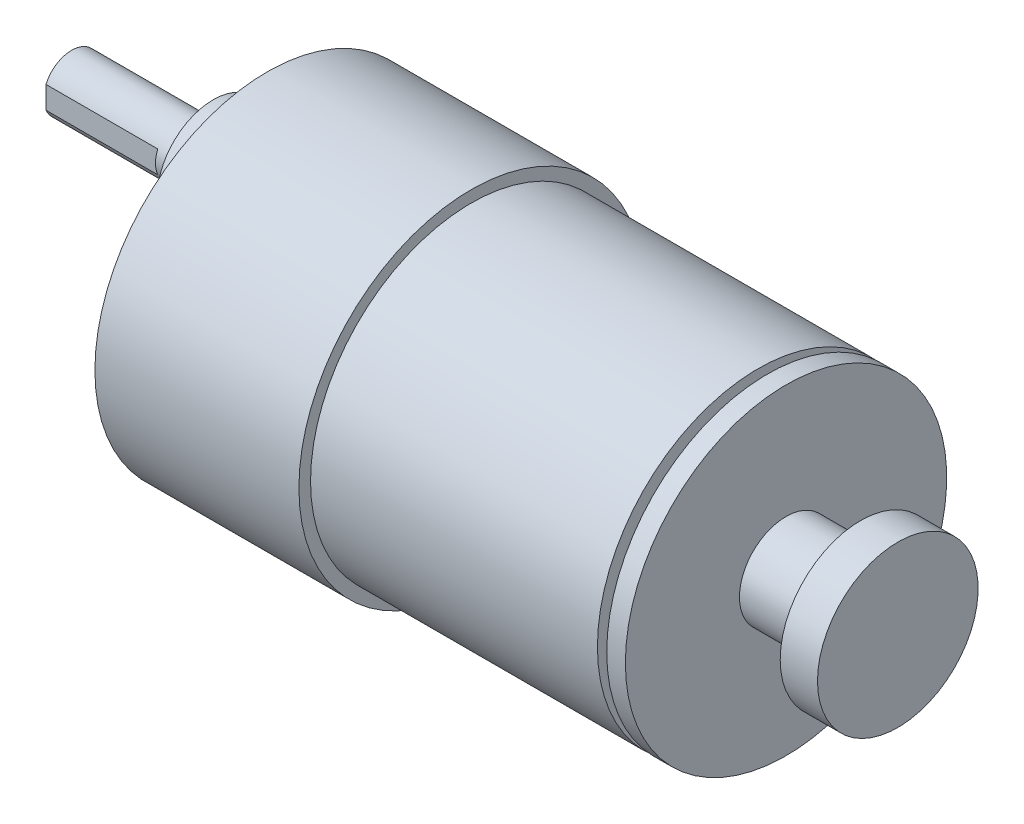
SolidWorks part; units mm, degrees
ref_plane "Front Plane" through (0, 0, 0) normal (0, 0, 1) x (1, 0, 0)
ref_plane "Top Plane" through (0, 0, 0) normal (0, 1, 0) x (1, 0, 0)
ref_plane "Right Plane" through (0, 0, 0) normal (1, 0, 0) x (0, 0, -1)
sketch "Sketch1" plane through (0, 0, 0) normal (0, 0, 1) x (1, 0, 0)
  line L0 (-80.1114, 0) -> (59.0183, 0) construction
  line L1 (0, 0) -> (0, 8.625)
  line L2 (0, 8.625) -> (-4, 8.625)
  line L3 (-4, 8.625) -> (-4, 5)
  line L4 (-4, 5) -> (-12, 5)
  line L5 (-12, 5) -> (-12, 17.25)
  line L6 (-12, 17.25) -> (-14, 17.25)
  line L7 (-14, 17.25) -> (-14, 5)
  line L8 (-14, 5) -> (-15, 5)
  line L9 (-15, 5) -> (-15, 17.25)
  line L10 (-15, 17.25) -> (-45.8, 17.25)
  line L11 (-45.8, 17.25) -> (-45.8, 18.5)
  line L12 (-45.8, 18.5) -> (-67.7, 18.5)
  line L13 (-67.7, 18.5) -> (-67.7, 0)
  line L14 (-67.7, 0) -> (0, 0)
  point P5 (0, 0)
  point P18 (0, 0)
  point P19 (0, 0)
  point P20 (0, 0)
  dimension "D1" = 34.5
  dimension "D2" = 30.8
  dimension "D3" = 37
  dimension "D4" = 21.9
  dimension "D5" = 15
  dimension "D6" = 17.25
  dimension "D7" = 1
  dimension "D8" = 2
  dimension "D9" = 10
  dimension "D10" = 4
revolve "MainBody" add sketch "Sketch1" angle 360 about L0
sketch "Sketch3" plane through (0, 0, 0) normal (0, 0, 1) x (1, 0, 0)
  line L0 (0, 0) -> (-101.2302, 0) construction
  line L1 (0, 7) -> (-101.2302, 7) construction
  line L2 (-67.7, 7) -> (-67.7, 13)
  line L4 (-67.7, 18.5) -> (-67.7, -18.5) construction
  line L5 (-67.7, 13) -> (-73.5, 13)
  line L6 (-73.5, 13) -> (-73.5, 10)
  line L7 (-73.5, 10) -> (-88.7, 10)
  line L8 (-88.7, 10) -> (-88.7, 7)
  line L9 (-88.7, 7) -> (-67.7, 7)
  dimension "D2" = 12
  dimension "D3" = 6
  dimension "D4" = 5.8
  dimension "D5" = 21
  dimension "D1" = 7
revolve "SmallBoss" add sketch "Sketch3" angle 360 about L1
sketch "Sketch4" plane through (-88.7, 0, 0) normal (-1, 0, 0) x (0, 0, 1)
  line L1 (-2.75, 10.7731) -> (2.75, 10.7731)
  line L2 (-2.75, 10.7731) -> (-2.75, 3.2269)
  line L3 (-2.75, 3.2269) -> (2.75, 3.2269)
  line L4 (2.75, 10.7731) -> (2.75, 3.2269)
  line L5 (-2.75, 10.7731) -> (2.75, 3.2269) construction
  line L6 (-2.75, 3.2269) -> (2.75, 10.7731) construction
  circle A0 centre (0, 7) radius 3 construction
  circle A1 centre (0, 7) radius 3
  point P0 (0, 7)
  point P1 (0, 7)
  circle M5 centre (0, 7) radius 3
  dimension "D1" = 5.5
extrude "Cut-Extrude1" cut sketch "Sketch4" against normal blind 12 contours L2 M5 | L4 M5 region at (-88.7, 7, -2.8504) region at (-88.7, 7, 2.8504)
hole_wizard "M3x0.5 Tapped Hole1" positions "Sketch7" profile "Sketch8" tap size "M3x0.5" standard "ANSI Metric"
sketch "Sketch7" plane through (-67.7, 0, 0) normal (-1, 0, 0) x (0, 0, 1)
  circle A0 centre (0, 0) radius 15.5 construction
  point P5 (15.5, 0)
  point P11 (7.75, -13.4234)
  point P12 (-7.75, -13.4234)
  point P13 (-15.5, 0)
  point P14 (-7.75, 13.4234)
  point P15 (7.75, 13.4234)
  dimension "D1" = 31
  dimension "D2" = 6
sketch "Sketch8" plane through (-67.7, 13.4234, 7.75) normal (0, 1, 0) x (0, 0, 1)
  line L0 (0, 0) -> (0, 9.2511)
  line L1 (0, 9.2511) -> (1.25, 8.5)
  line L2 (1.25, 8.5) -> (1.25, 0)
  line L5 (1.25, 0) -> (0, 0)
  line L10 (0, 9.2511) -> (-1.25, 8.5) construction
  line L11 (0, -6.35) -> (0, 107.95) construction
  dimension "Tap Drill Dia." = 2.5
  dimension "Tap Drill Depth" = 8.5
  dimension "Drill Angle" = 118
cosmetic thread "Hole Thread1" parameters "D1"=6, "D2"=3
cosmetic thread "Hole Thread2" parameters "D1"=6, "D2"=3
cosmetic thread "Hole Thread3" parameters "D1"=6, "D2"=3
cosmetic thread "Hole Thread4" parameters "D1"=6, "D2"=3
cosmetic thread "Hole Thread5" parameters "D1"=6, "D2"=3
cosmetic thread "Hole Thread6" parameters "D1"=6, "D2"=3
sketch "Sketch9" plane through (-67.7, 0, 0) normal (-1, 0, 0) x (0, 0, 1)
  circle A0 centre (0, 0) radius 11.3016
  circle A1 centre (0, 7) radius 9.3451
extrude "Cut-Extrude2" cut sketch "Sketch9" against normal blind 2 contours A1 A0 region at (-67.7, -4.1669, 0)
